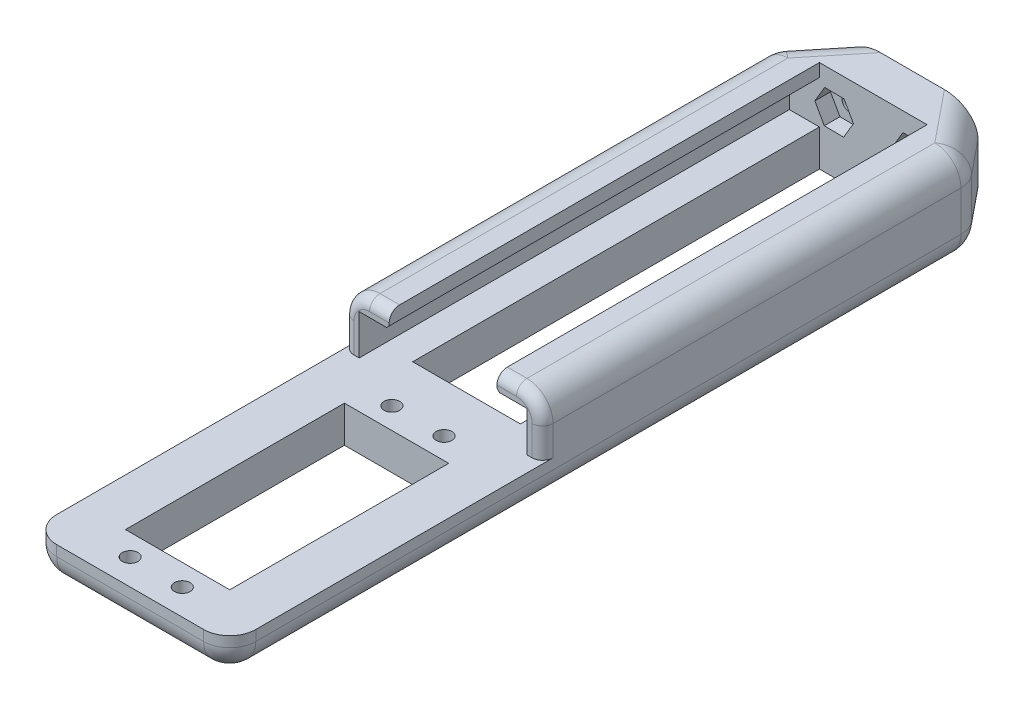
SolidWorks part; units mm, degrees
ref_plane "Front Plane" through (0, 0, 0) normal (0, 0, 1) x (1, 0, 0)
ref_plane "Top Plane" through (0, 0, 0) normal (0, 1, 0) x (1, 0, 0)
ref_plane "Right Plane" through (0, 0, 0) normal (1, 0, 0) x (0, 0, -1)
sketch "Sketch1" plane through (0, 0, 0) normal (0, 0, 1) x (1, 0, 0)
  line L0 (-69.7691, 23.4512) -> (-75.5286, 23.4512)
  line L1 (-75.5286, 23.4512) -> (-75.5286, 15.7512)
  line L2 (-75.5286, 15.7512) -> (-69.7691, 15.7512)
  line L3 (-69.7691, 15.7512) -> (-69.7691, 8.7512)
  line L4 (-69.7691, 8.7512) -> (-78.5286, 8.7512)
  line L5 (-78.5286, 8.7512) -> (-78.5286, 26.4512)
  line L6 (-78.5286, 26.4512) -> (-69.7691, 26.4512)
  line L7 (-69.7691, 26.4512) -> (-69.7691, 23.4512)
  line L8 (-49.1122, 23.4512) -> (-49.1122, 26.4512)
  line L9 (-49.1122, 26.4512) -> (-40.3527, 26.4512)
  line L10 (-40.3527, 26.4512) -> (-40.3527, 8.7512)
  line L11 (-40.3527, 8.7512) -> (-49.1122, 8.7512)
  line L12 (-49.1122, 8.7512) -> (-49.1122, 15.7512)
  line L13 (-49.1122, 15.7512) -> (-43.3527, 15.7512)
  line L14 (-43.3527, 15.7512) -> (-43.3527, 23.4512)
  line L15 (-43.3527, 23.4512) -> (-49.1122, 23.4512)
  dimension "D1" = 17.7
  dimension "D2" = 5.7594
  dimension "D3" = 20.657
  dimension "D4" = 7.7
  dimension "D8" = 3
  dimension "D9" = 3
extrude "Boss-Extrude1" add sketch "Sketch1" along normal blind 55 and the other way blind 35
sketch "Sketch2" plane through (0, 26.4512, 0) normal (0, 1, 0) x (1, 0, 0)
  line L0 (-40.3527, 35) -> (-40.3527, -55) construction
  line L6 (-78.5286, 35) -> (-40.3527, 35)
  line L7 (-78.5286, 35) -> (-78.5286, 27.5)
  line L8 (-78.5286, 27.5) -> (-40.3527, 27.5)
  line L9 (-40.3527, 35) -> (-40.3527, 27.5)
  dimension "D1" = 7.5
extrude "Boss-Extrude2" add sketch "Sketch2" against normal up to vertex (3 mm away) up to point (-69.7691, 23.4512, -35)
sketch "Sketch3" plane through (0, 8.7512, 0) normal (0, -1, 0) x (1, 0, 0)
  line L0 (-40.3527, -35) -> (-40.3527, 55) construction
  line L1 (-78.5286, 55) -> (-40.3527, 55)
  line L2 (-78.5286, 55) -> (-78.5286, 47.5)
  line L3 (-78.5286, 47.5) -> (-40.3527, 47.5)
  line L4 (-40.3527, 55) -> (-40.3527, 47.5)
  line L6 (-78.5286, -35) -> (-40.3527, -35)
  line L7 (-78.5286, -35) -> (-78.5286, -27.5)
  line L8 (-78.5286, -27.5) -> (-40.3527, -27.5)
  line L9 (-40.3527, -35) -> (-40.3527, -27.5)
  line L10 (-69.7691, -27.5) -> (-49.1122, -27.5) construction
extrude "Boss-Extrude3" add sketch "Sketch3" against normal up to vertex (7 mm away) up to point (-69.7691, 15.7512, 55)
ref_plane "MidSlide" through (0, 19.6012, 0) normal (0, 1, 0) x (1, 0, 0)
ref_plane "Plane2" through (-59.4407, 0, 0) normal (1, 0, 0) x (0, 0, -1)
sketch "Sketch11" plane through (0, 15.7512, 0) normal (0, 1, 0) x (1, 0, 0)
  line L0 (-49.4407, -84.9121) -> (-40.3527, -84.9121) construction
  line L1 (-40.3527, -115) -> (-78.5286, -115)
  line L2 (-40.3527, -115) -> (-40.3527, -55)
  line L3 (-40.3527, -55) -> (-78.5286, -55)
  line L4 (-78.5286, -115) -> (-78.5286, -55)
  line L5 (-49.4407, -105.9121) -> (-69.4407, -105.9121)
  line L6 (-49.4407, -105.9121) -> (-49.4407, -63.9121)
  line L7 (-49.4407, -63.9121) -> (-69.4407, -63.9121)
  line L8 (-69.4407, -105.9121) -> (-69.4407, -63.9121)
  line L9 (-69.4407, -84.9121) -> (-78.5286, -84.9121) construction
  line L10 (-59.4407, -105.9121) -> (-59.4407, -115) construction
  line L11 (-49.4407, -63.9121) -> (-49.4407, -59.8121) construction
  line L12 (-54.4407, -59.8121) -> (-54.4407, -63.9121) construction
  line L13 (-54.4407, -110.0121) -> (-54.4407, -105.9121) construction
  line L14 (-49.4407, -59.8121) -> (-54.4407, -59.8121) construction
  line L15 (-54.4407, -59.8121) -> (-64.4407, -59.8121) construction
  line L16 (-64.4407, -59.8121) -> (-69.4407, -59.8121) construction
  line L17 (-69.4407, -59.8121) -> (-69.4407, -63.9121) construction
  line L19 (-59.4407, -9.735) -> (-59.4407, 9.735) construction
  line L20 (-43.3527, -55) -> (-75.5286, -55) construction
  line L21 (-78.5286, 35) -> (-78.5286, -55) construction
  circle A0 centre (-54.4407, -110.0121) radius 1.5
  circle A1 centre (-64.4407, -110.0121) radius 1.5
  circle A2 centre (-54.4407, -59.8121) radius 1.5
  circle A3 centre (-64.4407, -59.8121) radius 1.5
  point P28 (-59.4407, -55)
  dimension "D5" = 10
  dimension "D4" = 3
  dimension "D1" = 60
  dimension "D2" = 20
  dimension "D3" = 42
  dimension "D6" = 4.1
extrude "Boss-Extrude7" add sketch "Sketch11" against normal blind 7
sketch "Sketch6" plane through (0, 0, -35) normal (0, 0, -1) x (-1, 0, 0)
  line L1 (43.3527, 23.4512) -> (75.5286, 23.4512)
  line L2 (43.3527, 23.4512) -> (43.3527, 15.7512)
  line L3 (43.3527, 15.7512) -> (75.5286, 15.7512)
  line L4 (75.5286, 23.4512) -> (75.5286, 15.7512)
  line L6 (43.3527, 23.4512) -> (43.3527, 15.7512) construction
  line L7 (43.3527, 15.7512) -> (75.5286, 15.7512) construction
  line L8 (75.5286, 23.4512) -> (43.3527, 23.4512) construction
  line L9 (75.5286, 15.7512) -> (75.5286, 23.4512) construction
sketch "Sketch7" plane through (0, 0, -35) normal (0, 0, -1) x (-1, 0, 0)
  line L0 (78.5286, 8.7512) -> (78.5286, 26.4512) construction
  line L1 (78.5286, 26.4512) -> (40.3527, 26.4512) construction
  line L2 (40.3527, 8.7512) -> (40.3527, 26.4512) construction
  line L3 (40.3527, 26.4512) -> (78.5286, 26.4512) construction
  line L4 (40.3527, 26.4512) -> (40.3527, 8.7512) construction
  line L5 (40.3527, 8.7512) -> (78.5286, 8.7512) construction
  line L6 (75.5286, 15.7512) -> (75.5286, 23.4512) construction
  line L7 (75.5286, 19.6012) -> (66.9407, 19.6012) construction
  line L8 (75.5286, 23.4512) -> (43.3527, 23.4512) construction
  line L9 (51.9407, 19.6012) -> (43.3527, 19.6012) construction
  line L10 (43.3527, 23.4512) -> (43.3527, 15.7512) construction
  circle A0 centre (66.9407, 19.6012) radius 1.5
  circle A1 centre (51.9407, 19.6012) radius 1.5
  dimension "D2" = 3
  dimension "D1" = 15
sketch "Sketch9" plane through (0, 26.4512, 0) normal (0, 1, 0) x (1, 0, 0)
  line L0 (-72.0286, 35) -> (-78.5286, 35)
  line L1 (-40.3527, 35) -> (-78.5286, 35) construction
  line L2 (-78.5286, 35) -> (-78.5286, 27)
  line L3 (-78.5286, 35) -> (-78.5286, -55) construction
  line L4 (-78.5286, 27) -> (-72.0286, 35)
  line L5 (-46.8527, 35) -> (-40.3527, 35)
  line L6 (-40.3527, 35) -> (-40.3527, 27)
  line L7 (-40.3527, -55) -> (-40.3527, 35) construction
  line L8 (-40.3527, 27) -> (-46.8527, 35)
  dimension "D1" = 8
  dimension "D2" = 6.5
ref_plane "Plane3" through (-40.3527, 26.4512, -35) normal (0, 0, -1) x (-1, 0, 0)
extrude "Boss-Extrude8" add sketch "Sketch6" against normal blind 7.5
extrude "Cut-Extrude1" cut sketch "Sketch9" against normal blind 18
extrude "Cut-Extrude2" cut sketch "Sketch7" against normal blind 10
sketch "Sketch14" plane through (0, 0, -27.5) normal (0, 0, 1) x (1, 0, 0)
  line L1 (-65.0515, 22.7829) -> (-68.7515, 22.8281)
  line L2 (-68.7515, 22.8281) -> (-70.6407, 19.6464)
  line L3 (-70.6407, 19.6464) -> (-68.8298, 16.4195)
  line L4 (-68.8298, 16.4195) -> (-65.1298, 16.3743)
  line L5 (-65.1298, 16.3743) -> (-63.2407, 19.556)
  line L6 (-63.2407, 19.556) -> (-65.0515, 22.7829)
  line L7 (-55.6407, 19.6464) -> (-53.8298, 16.4195)
  line L8 (-53.8298, 16.4195) -> (-50.1298, 16.3743)
  line L9 (-50.1298, 16.3743) -> (-48.2407, 19.556)
  line L10 (-48.2407, 19.556) -> (-50.0515, 22.7829)
  line L11 (-50.0515, 22.7829) -> (-53.7515, 22.8281)
  line L12 (-53.7515, 22.8281) -> (-55.6407, 19.6464)
  circle A0 centre (-66.9407, 19.6012) radius 3.2045 construction
  circle A1 centre (-51.9407, 19.6012) radius 3.2045 construction
  dimension "D1" = 3.7
extrude "Cut-Extrude3" cut sketch "Sketch14" against normal blind 3
chamfer "Chamfer1" distance 0.5 angle 45 2 edges at (-69.7691, 23.4512, 13.75) (-49.1122, 23.4512, 13.75)
chamfer "Chamfer2" distance 10 angle 45 1 edges at (-59.4407, 8.7512, 47.5)
fillet "Fillet38" radius 5 4 edges at (-40.3527, 8.7512, 44) (-78.5286, 26.4512, 14) (-40.3527, 26.4512, 14) (-78.5286, 8.7512, 44)
fillet "Fillet39" radius 5 5 edges at (-77.0641, 10.2156, 115) (-59.4407, 8.7512, 115) (-41.8172, 10.2156, 115) (-78.5286, 14.7512, 115) (-40.3527, 14.7512, 115)
fillet "Fillet40" radius 2 6 edges at (-71.6489, 26.4512, 55) (-47.2324, 26.4512, 55) (-77.0641, 24.9867, 55) (-41.8172, 24.9867, 55)
fillet "Fillet41" radius 5 10 edges at (-72.7786, 8.7512, -34.0769) (-77.0641, 10.2156, -28.8024) (-78.5286, 17.6012, -27) (-72.7786, 26.4512, -34.0769) (-46.1027, 26.4512, -34.0769) (-46.1027, 8.7512, -34.0769) (-41.8172, 10.2156, -28.8024) (-40.3527, 17.6012, -27) (-77.0641, 24.9867, -28.8024) (-41.8172, 24.9867, -28.8024)
